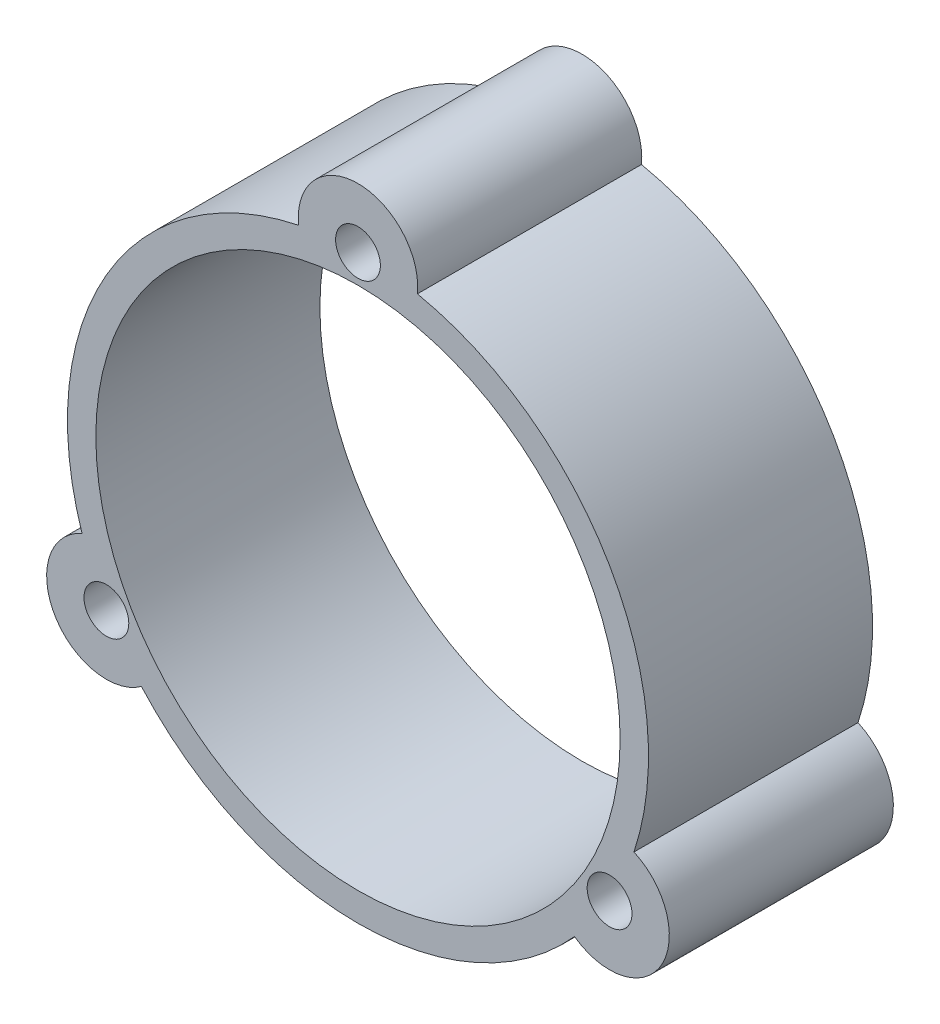
SolidWorks part; units mm, degrees
material "PLA"
ref_plane "Front" through (0, 0, 0) normal (0, 0, 1) x (1, 0, 0)
ref_plane "Top" through (0, 0, 0) normal (0, 1, 0) x (1, 0, 0)
ref_plane "Right" through (0, 0, 0) normal (1, 0, 0) x (0, 0, -1)
other "Configuration Table"
sketch "Esquisse1" plane through (0, 0, 0) normal (0, 0, 1) x (1, 0, 0)
  line L0 (0, 0) -> (0, 19.45) construction
  circle A0 centre (0, 19.45) radius 1.5
  circle A2 centre (0, 19.45) radius 4
  circle A3 centre (0, 0) radius 19.45
  circle A4 centre (0, 0) radius 17.25 construction
  circle A5 centre (0, 0) radius 17.55
  dimension "D1" = 3
  dimension "D2" = 8
  dimension "D3" = 38.9
  dimension "D4" = 34.5
  dimension "D5" = 0.3
extrude "Boss.-Extru.1" add sketch "Esquisse1" along normal blind 15 contours A5 A2 A3 | A5 A2 A3 A0 | A0 A3 region at (0, 18.8031, 0) region at (0, 17.8675, 0) region at (-4.2786, 17.9102, 0)
extrude "Enlèv. mat.-Extru.1" cut sketch "Esquisse1<5>" along normal up to surface (15 mm away) contours A0 up to face at (17.55, 0, 15)
sketch "Esquisse1<5>" plane through (0, 0, 0) normal (0, 0, 1) x (1, 0, 0) same geometry as "Esquisse1"
extrude "Boss.-Extru.2" add sketch "Esquisse1<6>" along normal up to surface (15 mm away) contours A3 A2 A0 region at (0, 21.2294, 0) up to face at (17.55, 0, 15)
sketch "Esquisse1<6>" plane through (0, 0, 0) normal (0, 0, 1) x (1, 0, 0) same geometry as "Esquisse1"
pattern_circular "Répétition circulaire1" count 2 every 120 about axis through (0, 0, 15) along (0, 0, -1) of "Boss.-Extru.2", "Enlèv. mat.-Extru.1" other way count 2
